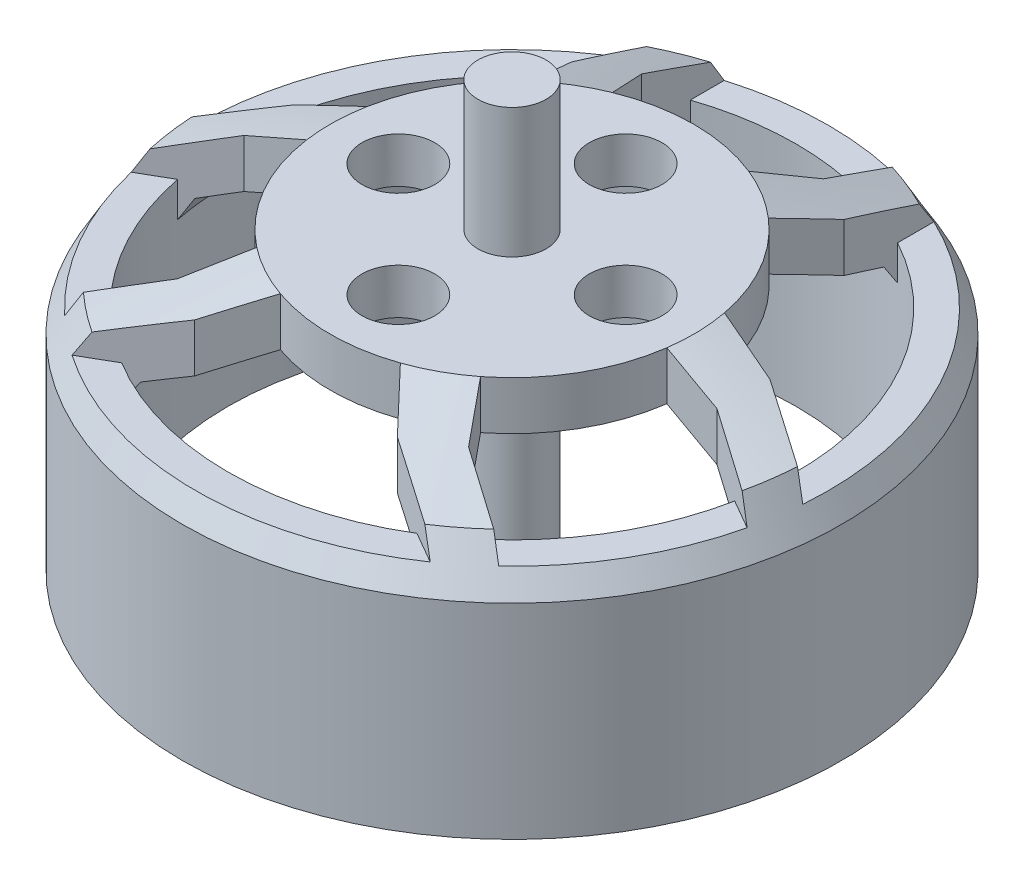
SolidWorks part; units mm, degrees
ref_plane "Front Plane" through (0, 0, 0) normal (0, 0, 1) x (1, 0, 0)
ref_plane "Top Plane" through (0, 0, 0) normal (0, 1, 0) x (1, 0, 0)
ref_plane "Right Plane" through (0, 0, 0) normal (1, 0, 0) x (0, 0, -1)
sketch "Sketch6" plane through (0, 0, 0) normal (0, 0, 1) x (1, 0, 0)
  line L0 (0, -0.306) -> (0, 13594.4415) construction
  line L1 (6.25, 0) -> (7.25, 0)
  line L2 (7.25, 0) -> (7.25, 4.5)
  line L3 (7.25, 4.5) -> (6.6726, 5.5)
  line L4 (6.6726, 5.5) -> (4, 6.5)
  line L5 (4, 6.5) -> (0, 6.5)
  line L6 (0, 6.5) -> (0, 5.5)
  line L7 (0, 5.5) -> (3.819, 5.5)
  line L8 (3.819, 5.5) -> (5.9861, 4.6892)
  line L9 (5.9861, 4.6892) -> (6.25, 4.2321)
  line L10 (6.25, 4.2321) -> (6.25, 0)
  point P2 (6.007, 5.1529)
  dimension "D1" = 8
  dimension "D2" = 14.5
  dimension "D3" = 30
  dimension "D4" = 2
  dimension "D5" = 1
  dimension "D6" = 4.5
  dimension "D7" = 1
  dimension "D8" = 1
  dimension "D9" = 1
  dimension "D10" = 1
revolve "Revolve1" add sketch "Sketch6" angle 360 about L0
sketch "Sketch7" plane through (0, 6.5, 0) normal (0, 1, 0) x (1, 0, 0)
  line L0 (2.6099, 3.0312) -> (3, 4.3084)
  line L1 (3, 4.3084) -> (3, 5.4829)
  line L2 (1.5, 3.7081) -> (2, 4.8541)
  line L3 (2, 4.8541) -> (2, 5.9214)
  line L4 (0, 0) -> (0, 50000) construction
  line L5 (-2.6099, 3.0312) -> (-3, 4.3084)
  line L6 (-3, 4.3084) -> (-3, 5.4829)
  line L7 (-1.5, 3.7081) -> (-2, 4.8541)
  line L8 (-2, 4.8541) -> (-2, 5.9214)
  line L9 (5.2038, -0.695) -> (6.128, -1.2286)
  line L10 (5.2312, 0.4439) -> (6.2484, -0.1434)
  line L11 (3.9301, 0.7446) -> (5.2312, 0.4439)
  line L12 (3.9613, -0.555) -> (5.2038, -0.695)
  line L13 (3.2038, -4.1591) -> (4.128, -4.6927)
  line L14 (2.2312, -4.7523) -> (3.2484, -5.3395)
  line L15 (1.3202, -3.7759) -> (2.2312, -4.7523)
  line L16 (2.4613, -3.1531) -> (3.2038, -4.1591)
  line L17 (-3.2038, -4.1591) -> (-4.128, -4.6927)
  line L18 (-2.2312, -4.7523) -> (-3.2484, -5.3395)
  line L19 (-1.3202, -3.7759) -> (-2.2312, -4.7523)
  line L20 (-2.4613, -3.1531) -> (-3.2038, -4.1591)
  line L21 (-5.2038, -0.695) -> (-6.128, -1.2286)
  line L22 (-5.2312, 0.4439) -> (-6.2484, -0.1434)
  line L23 (-3.9301, 0.7446) -> (-5.2312, 0.4439)
  line L24 (-3.9613, -0.555) -> (-5.2038, -0.695)
  circle A0 centre (0, 0) radius 6.25 construction
  arc A1 (-3, 5.4829) -> (-6.2484, -0.1434) centre (0, 0) ccw
  arc A3 (-6.128, -1.2286) -> (-4.128, -4.6927) centre (0, 0) ccw
  circle A4 centre (0, 0) radius 4 construction
  arc A5 (-3.9613, -0.555) -> (-2.4613, -3.1531) centre (0, 0) ccw
  circle A7 centre (0, 0) radius 5.25 construction
  arc A8 (-3.2484, -5.3395) -> (3.2484, -5.3395) centre (0, 0) ccw
  arc A9 (-1.3202, -3.7759) -> (1.3202, -3.7759) centre (0, 0) ccw
  arc A10 (2.4613, -3.1531) -> (3.9613, -0.555) centre (0, 0) ccw
  arc A11 (4.128, -4.6927) -> (6.128, -1.2286) centre (0, 0) ccw
  arc A12 (6.2484, -0.1434) -> (3, 5.4829) centre (0, 0) ccw
  arc A13 (3.9301, 0.7446) -> (2.6099, 3.0312) centre (0, 0) ccw
  arc A14 (-2.6099, 3.0312) -> (-3.9301, 0.7446) centre (0, 0) ccw
  arc A15 (1.5, 3.7081) -> (-1.5, 3.7081) centre (0, 0) ccw
  arc A16 (2, 5.9214) -> (-2, 5.9214) centre (0, 0) ccw
  point P19 (-6.8648, 0.1049)
  point P20 (0, 0)
  point P50 (0, 0)
  dimension "D5" = 1
  dimension "D2" = 6
  dimension "D3" = 1
  dimension "D4" = 1.3
  dimension "D6" = 3
  dimension "D7" = 3
extrude "Cut-Extrude3" cut sketch "Sketch7" against normal through all
sketch "Sketch8" plane through (0, 6.5, 0) normal (0, 1, 0) x (1, 0, 0)
  line L0 (3, 5.4829) -> (3, 6.6002)
  line L1 (6.2484, -0.1434) -> (7.2159, -0.702)
  line L2 (6.2484, -0.1434) -> (5.2312, 0.4439) construction
  circle A0 centre (0, 0) radius 6.25 construction
  circle A1 centre (0, 0) radius 7.25
  arc A2 (7.2159, -0.702) -> (3, 6.6002) centre (0, 0) ccw
  arc A3 (6.2484, -0.1434) -> (3, 5.4829) centre (0, 0) ccw
  dimension "D1" = 0
extrude "Cut-Extrude4" cut sketch "Sketch8" against normal blind 1.5
sketch "Sketch9" plane through (0, 6.5, 0) normal (0, 1, 0) x (1, 0, 0)
  line L0 (-2, 5.9214) -> (-2, 6.7082)
  line L1 (2, 5.9214) -> (2, 6.7082)
  arc A3 (2, 5.9214) -> (-2, 5.9214) centre (0, 0) ccw construction
  arc A4 (2, 5.9214) -> (-2, 5.9214) centre (0, 0) ccw
  arc A7 (2, 6.7082) -> (-2, 6.7082) centre (0, 0) ccw
  circle A8 centre (0, 0) radius 7.25 construction
  dimension "D1" = 0.25
extrude "Cut-Extrude5" cut sketch "Sketch9" against normal up to surface (1.5 mm away) up to face at (5.2589, 5, -3.0362)
pattern_circular "CirPattern1" count 3 over 360 about axis through (0, -0.306, 0) along (0, -1, 0) of "Cut-Extrude4", "Cut-Extrude5" reverse direction yes
sketch "Sketch10" plane through (0, 6.5, 0) normal (0, 1, 0) x (1, 0, 0)
  circle A0 centre (0, 0) radius 0.75
  dimension "D1" = 1.5
extrude "Boss-Extrude4" add sketch "Sketch10" against normal blind 13.55 from offset 2.85
hole_wizard "M2x0.4 Tapped Hole1" positions "Sketch11" profile "Sketch13" tap size "M2x0.4" standard "ANSI Metric" end condition through all
sketch "Sketch11" plane through (0, 6.5, 0) normal (0, 1, 0) x (1, 0, 0)
  circle A0 centre (0, 0) radius 2.5
  point P0 (0, 2.5)
  point P2 (2.5, 0)
  point P4 (0, -2.5)
  point P6 (-2.5, 0)
  point P13 (2.1046, 0)
  point P14 (0, 2.1046)
  point P15 (-2.1046, 0)
  point P16 (0, -2.1046)
  dimension "D1" = 5
sketch "Sketch13" plane through (0, 6.5, -2.5) normal (1, 0, 0) x (0, 0, 1)
  line L0 (0, 0) -> (0, 10.7)
  line L1 (0, 10.7) -> (0.8, 10.7)
  line L2 (0.8, 10.7) -> (0.8, 0)
  line L5 (0.8, 0) -> (0, 0)
  line L11 (0, -6.35) -> (0, 107.95) construction
  dimension "Thru Tap Drill Dia." = 1.6
  dimension "Thru Tap Drill Depth" = 10.7
cosmetic thread "Hole Thread1" parameters "D2"=2
cosmetic thread "Hole Thread2" parameters "D2"=2
cosmetic thread "Hole Thread3" parameters "D2"=2
cosmetic thread "Hole Thread4" parameters "D2"=2
